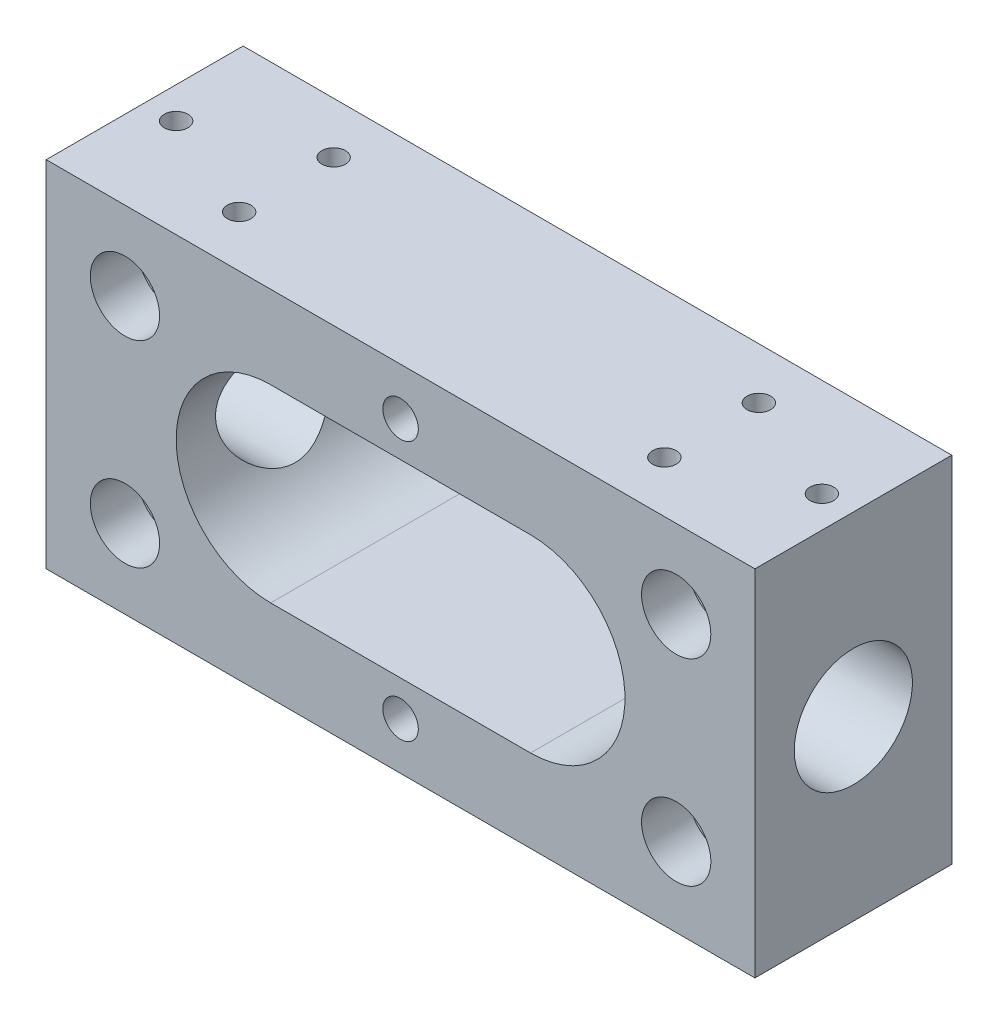
SolidWorks part; units mm, degrees
material "6061-T4 (SS)"
ref_plane "Piano frontale" through (0, 0, 0) normal (0, 0, 1) x (1, 0, 0)
ref_plane "Piano superiore" through (0, 0, 0) normal (0, 1, 0) x (1, 0, 0)
ref_plane "Piano destro" through (0, 0, 0) normal (1, 0, 0) x (0, 0, -1)
sketch "Schizzo1" plane through (0, 0, 0) normal (0, 0, 1) x (1, 0, 0)
  line L1 (0, 0) -> (90, 0)
  line L2 (0, 0) -> (0, 45)
  line L3 (0, 45) -> (90, 45)
  line L4 (90, 0) -> (90, 45)
  dimension "D1" = 90
  dimension "D2" = 45
extrude "Estrusione-Estrusione1" add sketch "Schizzo1" against normal blind 25
sketch "Schizzo2" plane through (0, 0, 0) normal (-1, 0, 0) x (0, 0, 1)
  line L0 (-25, 22.5) -> (0, 22.5) construction
  line L1 (-25, 45) -> (-25, 0) construction
  line L2 (0, 45) -> (0, 0) construction
  circle A0 centre (-12.5, 22.5) radius 7.5
  dimension "D1" = 15
extrude "Taglio-Estrusione1" cut sketch "Schizzo2" against normal through all
sketch "Schizzo3" plane through (0, 0, -25) normal (0, 0, -1) x (-1, 0, 0)
  line L0 (-94.314, 39) -> (4.9562, 39) construction
  line L2 (-90, 45) -> (0, 45) construction
  line L4 (-90, 22.5) -> (0, 22.5) construction
  line L5 (-90, 0) -> (-90, 45) construction
  line L6 (0, 45) -> (0, 0) construction
  line L7 (-94.314, 6) -> (4.9562, 6) construction
  line L8 (-45, 45) -> (-45, 0) construction
  line L9 (0, 0) -> (-90, 0) construction
  point P16 (-45, 39)
  point P17 (-45, 6)
  dimension "D1" = 6
hole_wizard "Foro lamato per Vite M4 a testa cilindrica piana-1" positions "Schizzo3D1" profile "Schizzo4" counterbore size "M4" standard "ISO" end condition through all
sketch3d "Schizzo3D1"
  point P0 (45, 39, -25)
  point P3 (45, 6, -25)
sketch "Schizzo4" plane through (45, 39, -25) normal (1, 0, 0) x (0, 1, 0)
  line L0 (0, 0) -> (0, 25)
  line L1 (0, 25) -> (2.25, 25)
  line L3 (2.25, 25) -> (2.25, 2.6)
  line L4 (2.25, 2.6) -> (4, 2.6)
  line L5 (4, 2.6) -> (4, 0)
  line L7 (4, 0) -> (0, 0)
  line L11 (0, -6.35) -> (0, 107.95) construction
  dimension "Thru Hole Dia." = 4.5
  dimension "Thru Hole Depth" = 25
  dimension "C'Bore Dia." = 8
  dimension "C'Bore Depth" = 2.6
ref_axis "Assi1" through (90, 22.5, -12.5) along (-1, 0, 0)
sketch "Schizzo14" plane through (0, 0, 0) normal (0, 0, 1) x (1, 0, 0)
  line L0 (45, 45) -> (45, 0) construction
  line L3 (61.5, 22.5) -> (28.5, 22.5) construction
  line L4 (90, 22.5) -> (0, 22.5) construction
  line L5 (61.5, 10.5) -> (28.5, 10.5)
  line L6 (61.5, 34.5) -> (28.5, 34.5)
  arc A0 (61.5, 10.5) -> (61.5, 34.5) centre (61.5, 22.5) ccw
  arc A1 (28.5, 34.5) -> (28.5, 10.5) centre (28.5, 22.5) ccw
  point P2 (45, 22.5)
  point P10 (45, 22.5)
  dimension "D1" = 33
  dimension "D2" = 24
extrude "Taglio-Estrusione4" cut sketch "Schizzo14" against normal through all
sketch "Schizzo15" plane through (0, 0, 0) normal (0, 0, 1) x (1, 0, 0)
  line L2 (0, 45) -> (0, 0) construction
  line L4 (45, 0) -> (45, 45) construction
  line L5 (90, 45) -> (0, 45) construction
  line L6 (0, 22.5) -> (90, 22.5) construction
  circle A0 centre (10, 10) radius 4.4
  circle A1 centre (80, 10) radius 4.4
  circle A2 centre (80, 35) radius 4.4
  circle A3 centre (10, 35) radius 4.4
  dimension "D1" = 8.8
  dimension "D2" = 10
  dimension "D3" = 10
extrude "Taglio-Estrusione5" cut sketch "Schizzo15" against normal blind 6
sketch "Schizzo16" plane through (0, 0, -6) normal (0, 0, 1) x (1, 0, 0)
  line L0 (45, 45) -> (45, 0) construction
  line L1 (0, 22.5) -> (90, 22.5) construction
  line L2 (0, 45) -> (0, 0) construction
  circle A0 centre (10, 10) radius 3
  circle A1 centre (80, 10) radius 3
  circle A2 centre (80, 35) radius 3
  circle A3 centre (10, 35) radius 3
  dimension "D1" = 6
extrude "Taglio-Estrusione6" cut sketch "Schizzo16" against normal through all
sketch "Schizzo17" plane through (0, 0, -25) normal (0, 0, -1) x (-1, 0, 0)
  line L0 (-45, 45) -> (-45, 0.5122) construction
  line L1 (-90, 45) -> (0, 45) construction
  line L2 (-45, 45) -> (-45, 0) construction
  line L3 (0, 22.5) -> (-90, 22.5) construction
  circle A0 centre (-10, 10) radius 5
  circle A1 centre (-80, 10) radius 5
  circle A2 centre (-80, 35) radius 5
  circle A3 centre (-10, 35) radius 5
  dimension "D1" = 10
extrude "Taglio-Estrusione8" cut sketch "Schizzo17" against normal blind 10
sketch "Schizzo18" plane through (0, 45, 0) normal (0, 1, 0) x (1, 0, 0)
  line L0 (0, 12.5) -> (90, 12.5) construction
  line L1 (0, 25) -> (0, 0) construction
  line L2 (90, 25) -> (90, 0) construction
  line L3 (45, 25) -> (45, 0) construction
  line L4 (90, 25) -> (0, 25) construction
  line L5 (90, 0) -> (0, 0) construction
  point P0 (4, 12.5)
  point P1 (18, 18.5)
  point P4 (18, 6.5)
  point P5 (72, 6.5)
  point P16 (72, 18.5)
  point P17 (86, 12.5)
  dimension "D3" = 6
  dimension "D1" = 4
  dimension "D2" = 18
hole_wizard "Foro Ø3.0 (3)-1" positions "Schizzo3D2" profile "Schizzo19" hole size "Ø3.0" standard "ISO"
sketch3d "Schizzo3D2"
  point P0 (18, 45, -18.5)
  point P3 (18, 45, -6.5)
  point P6 (4, 45, -12.5)
  point P9 (72, 45, -18.5)
  point P12 (72, 45, -6.5)
  point P15 (86, 45, -12.5)
sketch "Schizzo19" plane through (18, 45, -18.5) normal (1, 0, 0) x (0, 0, 1)
  line L0 (0, 0) -> (0, 12.9013)
  line L1 (0, 12.9013) -> (1.5, 12)
  line L2 (1.5, 12) -> (1.5, 0)
  line L5 (1.5, 0) -> (0, 0)
  line L10 (0, 12.9013) -> (-1.5, 12) construction
  line L11 (0, -6.35) -> (0, 107.95) construction
  dimension "Hole Dia." = 3
  dimension "Hole Depth" = 12
  dimension "Drill Angle" = 118
sketch "Schizzo20" plane through (0, 0, 0) normal (0, -1, 0) x (1, 0, 0)
  line L0 (0, -12.5) -> (90, -12.5) construction
  line L1 (45, 0) -> (45, -25) construction
  point P8 (4, -12.5)
  point P9 (18, -6.5)
  point P11 (18, -18.5)
  point P13 (72, -6.5)
  point P15 (86, -12.5)
  point P17 (72, -18.5)
  point P19 (-24.9919, -2.1046)
hole_wizard "Foro Ø3.0 (3)-2" positions "Schizzo3D3" profile "Schizzo21" hole size "Ø3.0" standard "ISO"
sketch3d "Schizzo3D3"
  point P0 (18, 0, -6.5)
  point P3 (4, 0, -12.5)
  point P6 (18, 0, -18.5)
  point P9 (72, 0, -6.5)
  point P12 (72, 0, -18.5)
  point P15 (86, 0, -12.5)
sketch "Schizzo21" plane through (18, 0, -6.5) normal (1, 0, 0) x (0, 0, -1)
  line L0 (0, 0) -> (0, 12.9013)
  line L1 (0, 12.9013) -> (1.5, 12)
  line L2 (1.5, 12) -> (1.5, 0)
  line L5 (1.5, 0) -> (0, 0)
  line L10 (0, 12.9013) -> (-1.5, 12) construction
  line L11 (0, -6.35) -> (0, 107.95) construction
  dimension "Hole Dia." = 3
  dimension "Hole Depth" = 12
  dimension "Drill Angle" = 118
sketch "Schizzo22" plane through (0, 0, 0) normal (-1, 0, 0) x (0, 0, 1)
  line L0 (-20, 45) -> (-20, 0) construction
  line L1 (-25, 45) -> (0, 45) construction
  line L2 (-25, 0) -> (0, 0) construction
  circle A0 centre (-12.5, 22.5) radius 7.5 construction
  point P5 (-20, 41)
  point P6 (-20, 4)
  dimension "D1" = 4
  dimension "D2" = 4
hole_wizard "Foro Ø3.0 (3)-3" positions "Schizzo3D4" profile "Schizzo23" hole size "Ø3.0" standard "ISO"
sketch3d "Schizzo3D4"
  point P0 (0, 41, -20)
  point P3 (0, 4, -20)
sketch "Schizzo23" plane through (0, 41, -20) normal (0, 1, 0) x (0, 0, 1)
  line L0 (0, 0) -> (0, 12.9013)
  line L1 (0, 12.9013) -> (1.5, 12)
  line L2 (1.5, 12) -> (1.5, 0)
  line L5 (1.5, 0) -> (0, 0)
  line L10 (0, 12.9013) -> (-1.5, 12) construction
  line L11 (0, -6.35) -> (0, 107.95) construction
  dimension "Hole Dia." = 3
  dimension "Hole Depth" = 12
  dimension "Drill Angle" = 118
